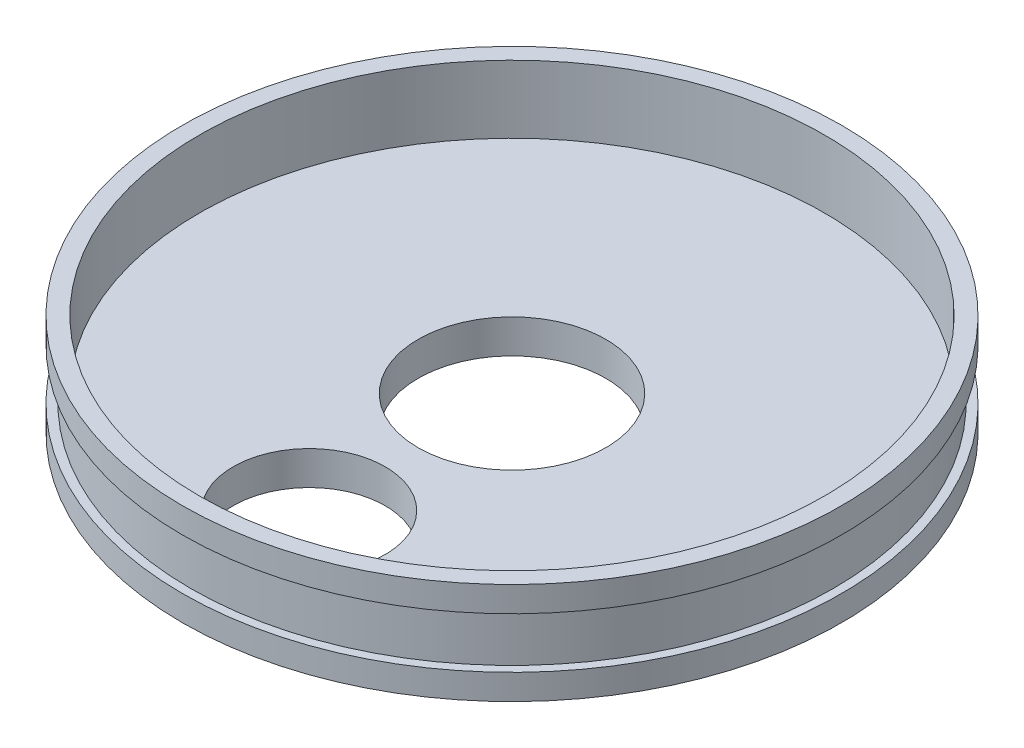
SolidWorks part; units mm, degrees
ref_plane "Front Plane" through (0, 0, 0) normal (0, 0, 1) x (1, 0, 0)
ref_plane "Top Plane" through (0, 0, 0) normal (0, 1, 0) x (1, 0, 0)
ref_plane "Right Plane" through (0, 0, 0) normal (1, 0, 0) x (0, 0, -1)
sketch "Sketch2" plane through (0, 0, 0) normal (0, 1, 0) x (1, 0, 0)
  line L0 (0, 0) -> (0, -12) construction
  circle A0 centre (0, 0) radius 18.5
  circle A1 centre (0, 0) radius 19.5
  circle A2 centre (0, 0) radius 17.5 construction
  circle A3 centre (0, -12) radius 4.5
  circle A4 centre (0, 0) radius 5.5562
  dimension "D1" = 37
  dimension "D2" = 39
  dimension "D3" = 35
  dimension "D5" = 9
  dimension "D6" = 11.1125
  dimension "D4" = 12
extrude "LidBase" add sketch "Sketch2" along normal blind 2 contours A1 A0 | A0 A3 region at (-17.9767, 0, 0) region at (-18.9485, 0, 0)
extrude "LidWalls" add sketch "Sketch2<4>" along normal blind 6 contours A1 A0 region at (-18.9485, 0, 0)
sketch "Sketch2<4>" plane through (0, 0, 0) normal (0, 1, 0) x (1, 0, 0) same geometry as "Sketch2"
sketch "Sketch3" plane through (0, 0, 0) normal (1, 0, 0) x (0, 0, -1)
  line L0 (0, 0) -> (0, 6) construction
  line L1 (19, 4.5) -> (19.5, 4.5)
  line L2 (18.5, 6) -> (-18.5, 6) construction
  line L3 (0, 0) -> (19.5, 0) construction
  line L4 (19.5, 0) -> (19.5, 1.5) construction
  line L5 (19.5, 1.5) -> (19, 1.5)
  line L6 (19, 1.5) -> (19, 4.5)
  line L7 (19.5, 4.5) -> (19.5, 1.5)
  line L9 (19.5, 0) -> (19.5, 6) construction
  line L11 (19.5, 6) -> (0, 6) construction
  dimension "D1" = 6
  dimension "D2" = 1.5
  dimension "D3" = 0.5
  dimension "D4" = 3
revolve "Beltgrooves" cut sketch "Sketch3" angle 360 about L0
